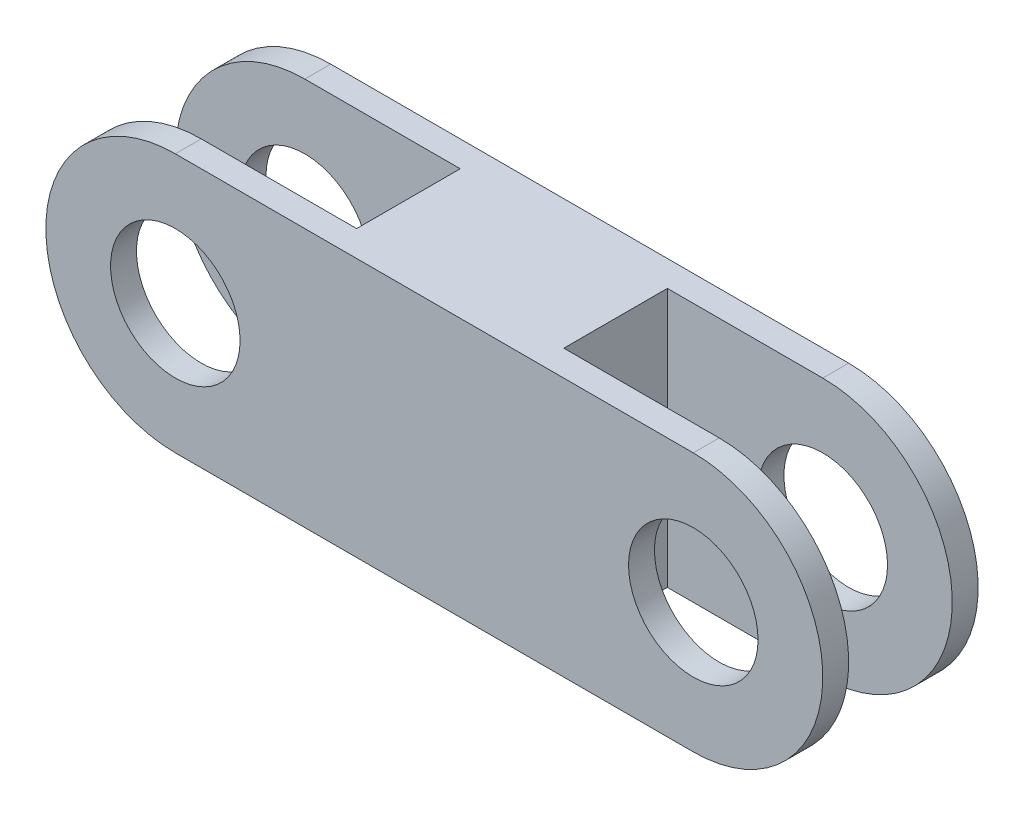
SolidWorks part; units mm, degrees
material "Alloy Steel"
ref_plane "Front Plane" through (0, 0, 0) normal (0, 0, 1) x (1, 0, 0)
ref_plane "Top Plane" through (0, 0, 0) normal (0, 1, 0) x (1, 0, 0)
ref_plane "Right Plane" through (0, 0, 0) normal (1, 0, 0) x (0, 0, -1)
other "Configuration Table"
sketch "Sketch1" plane through (0, 0, 0) normal (0, 0, 1) x (1, 0, 0)
  line L0 (0, 0) -> (20, 0) construction
  line L1 (0, 5) -> (20, 5)
  line L2 (0, -5) -> (20, -5)
  line L3 (10, 0) -> (10, 30.2937) construction
  arc A0 (0, 5) -> (0, -5) centre (0, 0) ccw
  arc A1 (20, -5) -> (20, 5) centre (20, 0) ccw
  circle A2 centre (0, 0) radius 2.5
  circle A3 centre (20, 0) radius 2.5
  circle A4 centre (10, -3) radius 1.25 construction
  point P3 (10, 0)
  dimension "D3" = 5
  dimension "D4" = 5
  dimension "D5" = 2.5
  dimension "D1" = 20
  dimension "D2" = 10
  dimension "D6" = 3
extrude "Boss-Extrude1" add sketch "Sketch1" along normal mid plane 6
ref_axis "Axis1" through (0, 0, 3) along (0, 0, -1)
ref_axis "Axis2" through (20, 0, 3) along (0, 0, -1)
sketch "Sketch2" plane through (0, 5, 0) normal (0, 1, 0) x (1, 0, 0)
  line L0 (0, 0) -> (20, 0) construction
  line L1 (10, 0) -> (10, 4.9864) construction
  line L3 (-14, 2) -> (6, 2)
  line L4 (-14, 2) -> (-14, -2)
  line L5 (-14, -2) -> (6, -2)
  line L6 (6, 2) -> (6, -2)
  line L7 (20, -3) -> (20, 3) construction
  dimension "D1" = 4
  dimension "D2" = 4
  dimension "D3" = 20
extrude "Cut-Extrude1" cut sketch "Sketch2" against normal through all
ref_plane "Plane1" through (10, 0, 0) normal (1, 0, 0) x (0, 0, -1)
mirror "Mirror1" about plane through (10, 0, 0) normal (1, 0, 0) of "Cut-Extrude1"
sketch3d "3DSketch1"
  line L0 (0, 0, 3) -> (0, 0, 2) construction
  line L1 (0, 0, 3) -> (0, 0, 2) construction
  line L2 (0, 0, -2) -> (0, 0, -3) construction
  line L3 (0, 0, -2) -> (0, 0, -3) construction
  line L4 (20, 0, -2) -> (20, 0, -3) construction
  line L5 (20, 0, 3) -> (20, 0, 2) construction
  line L6 (20, 0, 3) -> (20, 0, -3) construction
  point P0 (0, 0, 3)
  point P1 (0, 0, -3)
  point P6 (20, 0, -3)
  point P11 (20, 0, 3)
  point P14 (0, 0, 0)
ref_point "Point1"
ref_point "Point2"
ref_point "Point3"
ref_point "Point4"
ref_plane "Plane2" through (20, 0, 0) normal (1, 0, 0) x (0, 0, -1)
